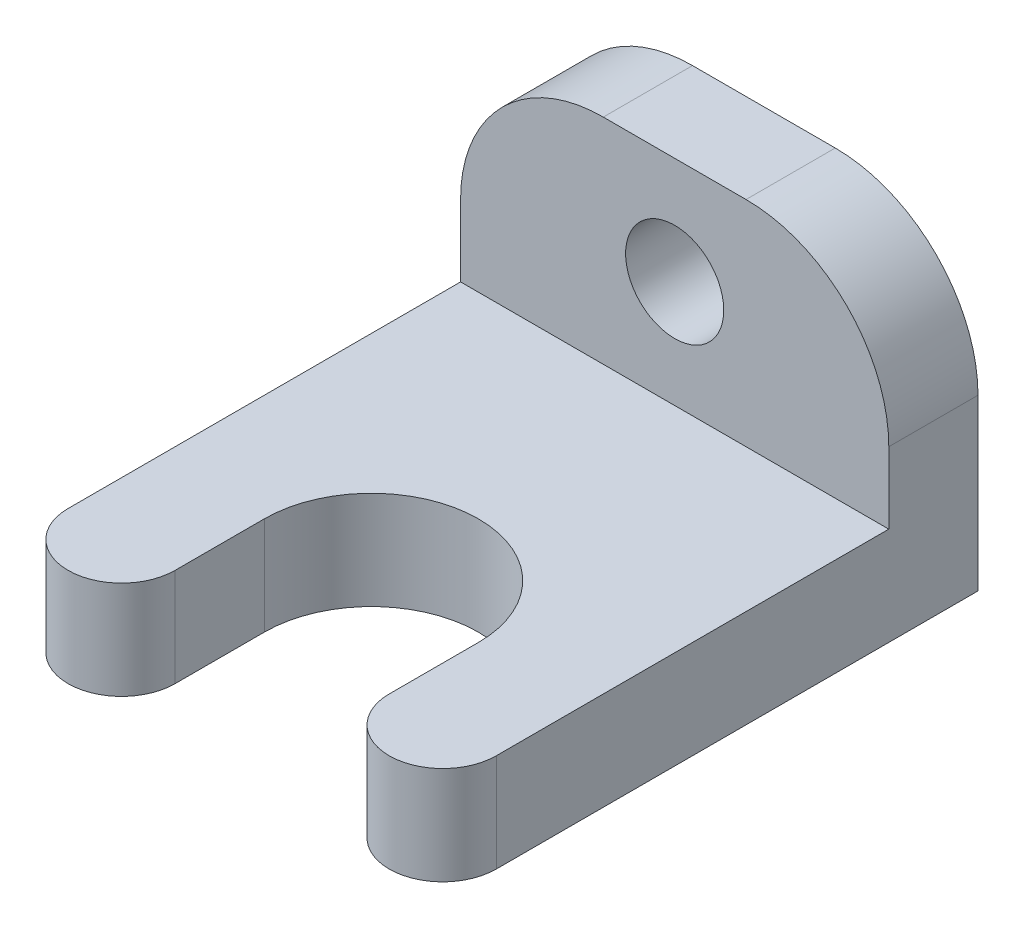
SolidWorks part; units mm, degrees
ref_plane "Front" through (0, 0, 0) normal (0, 0, 1) x (1, 0, 0)
ref_plane "Top" through (0, 0, 0) normal (0, 1, 0) x (1, 0, 0)
ref_plane "Right" through (0, 0, 0) normal (1, 0, 0) x (0, 0, -1)
sketch "Sketch2" plane through (0, 0, 0) normal (0, 1, 0) x (1, 0, 0)
  line L0 (0, 0) -> (0, -22) construction
  line L1 (12, 22) -> (-12, 22)
  line L2 (12, 22) -> (12, -22)
  line L3 (12, -22) -> (-12, -22)
  line L4 (-12, 22) -> (-12, -22)
  line L5 (0, -22) -> (0, 22) construction
  line L6 (12, 0) -> (-12, 0) construction
  line L7 (6, 0) -> (6, -22)
  line L8 (-6, 0) -> (-6, -22)
  arc A0 (6, 0) -> (-6, 0) centre (0, 0) ccw
  arc A1 (-6, -22) -> (6, -22) centre (0, -22) ccw
  point P0 (0, 0)
  point P6 (0, -11)
  point P11 (0, 0)
  dimension "D1" = 12
  dimension "D2" = 22
  dimension "D3" = 12
extrude "Boss-Extrude1" add sketch "Sketch2" along normal blind 5.5 contours L4 L3 L2 L1
extrude "Cut-Extrude1" cut sketch "Sketch2<3>" along normal through all contours A1 L7 A0 L8
sketch "Sketch2<3>" plane through (0, 0, 0) normal (0, 1, 0) x (1, 0, 0) same geometry as "Sketch2"
sketch "Sketch3" plane through (0, 5.5, 0) normal (0, 1, 0) x (1, 0, 0)
  line L0 (12, 22) -> (12, -22) construction
  line L1 (-12, 22) -> (12, 22)
  line L2 (-12, 22) -> (-12, 17)
  line L3 (-12, 17) -> (12, 17)
  line L4 (12, 22) -> (12, 17)
  line L5 (0, 17) -> (0, 22) construction
  line L6 (-12, 19.5) -> (12, 19.5) construction
  point P140 (0, 19.5)
  dimension "D1" = 5
extrude "Boss-Extrude2" add sketch "Sketch3" along normal blind 12
hole_wizard "M5 Clearance Hole1" positions "Sketch4" profile "Sketch5" hole size "M5" standard "ANSI Metric" end condition through all
sketch "Sketch4" plane through (0, 0, -17) normal (0, 0, 1) x (1, 0, 0)
  line L0 (-12, 11.5) -> (0, 11.5) construction
  line L1 (-12, 17.5) -> (-12, 5.5) construction
  point P0 (0, 11.5)
  point P8 (0, 0)
sketch "Sketch5" plane through (0, 11.5, -17) normal (1, 0, 0) x (0, -1, 0)
  line L0 (0, 0) -> (0, 5)
  line L1 (0, 5) -> (2.75, 5)
  line L2 (2.75, 5) -> (2.75, 0)
  line L5 (2.75, 0) -> (0, 0)
  line L11 (0, -6.35) -> (0, 107.95) construction
  dimension "Thru Hole Dia." = 5.5
  dimension "Thru Hole Depth" = 5
fillet "Fillet1" radius 8 2 edges at (12, 17.5, -19.5) (-12, 17.5, -19.5)
sketch "Sketch6" plane through (0, 5.5, 0) normal (0, 1, 0) x (1, 0, 0)
  line L0 (12, 22) -> (12, -22) construction
  line L1 (-12, -22) -> (12, -22)
  line L2 (-12, -22) -> (-12, -8)
  line L3 (-12, -8) -> (12, -8)
  line L4 (12, -22) -> (12, -8)
  line L5 (0, -8) -> (0, -22) construction
  line L6 (-12, -15) -> (12, -15) construction
  point P200 (0, -15)
  dimension "D1" = 8
extrude "Cut-Extrude2" cut sketch "Sketch6" against normal through all
fillet "Fillet2" 2 edges at (-6, 2.75, 8) (-12, 2.75, 8) type full round first side face at (-6, 2.75, 4) second side face at (-12, 5, -10.3333) middle face at (-9, 2.75, 8)
fillet "Fillet3" 2 edges at (6, 2.75, 8) (12, 2.75, 8) type full round first side face at (6, 2.75, 4) second side face at (12, 5, -10.3333) middle face at (9, 2.75, 8)
